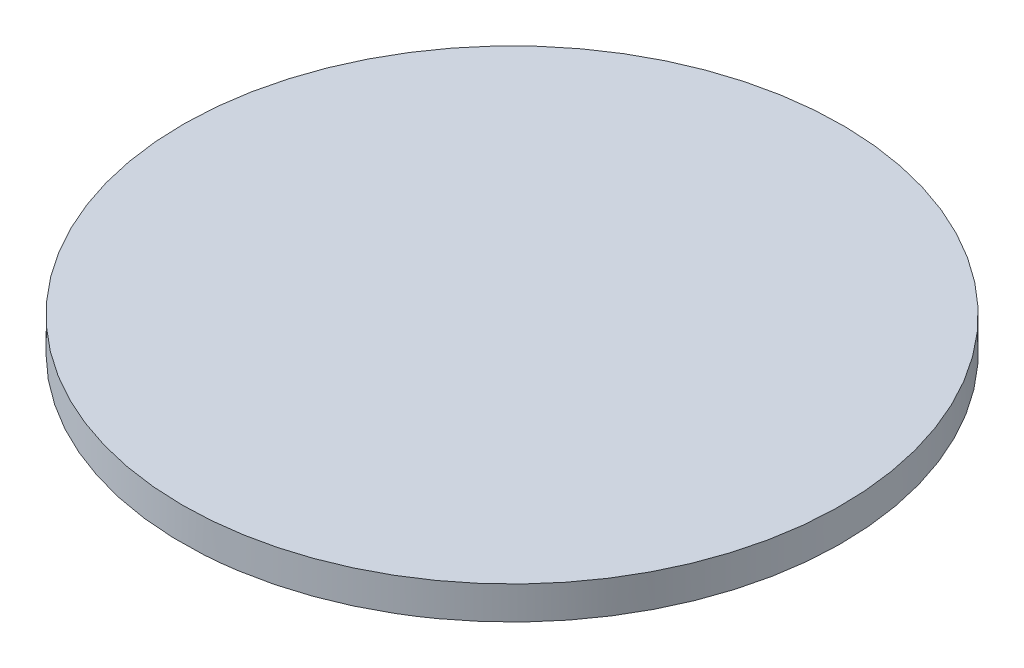
SolidWorks part; units mm, degrees
material "AISI 1020"
ref_plane "Front Plane" through (0, 0, 0) normal (0, 0, 1) x (1, 0, 0)
ref_plane "Top Plane" through (0, 0, 0) normal (0, 1, 0) x (1, 0, 0)
ref_plane "Right Plane" through (0, 0, 0) normal (1, 0, 0) x (0, 0, -1)
sketch "Sketch1" plane through (0, 0, 0) normal (0, 1, 0) x (1, 0, 0)
  circle A0 centre (0, 0) radius 110
  dimension "D1" = 220
extrude "Boss-Extrude1" add sketch "Sketch1" along normal blind 293
sketch "Sketch2" plane through (0, 293, 0) normal (0, 1, 0) x (1, 0, 0)
  circle A0 centre (0, 0) radius 42.5
  dimension "D1" = 85
extrude "Boss-Extrude2" add sketch "Sketch2" along normal blind 10
sketch "Sketch3" plane through (0, 303, 0) normal (0, 1, 0) x (1, 0, 0)
  circle A0 centre (0, 0) radius 44.5
  dimension "D1" = 89
extrude "Boss-Extrude3" add sketch "Sketch3" along normal blind 600
sketch "Sketch4" plane through (0, 903, 0) normal (0, 1, 0) x (1, 0, 0)
  circle A0 centre (0, 0) radius 1500
  dimension "D1" = 3000
extrude "Boss-Extrude4" add sketch "Sketch4" along normal blind 150
loft "Loft1" add section edge at (0, 903, 1500) section edge at (0, 303, 44.5) connector at (506.333, 903, 1411.9585) connector at (-12.9511, 303, 42.5737)
